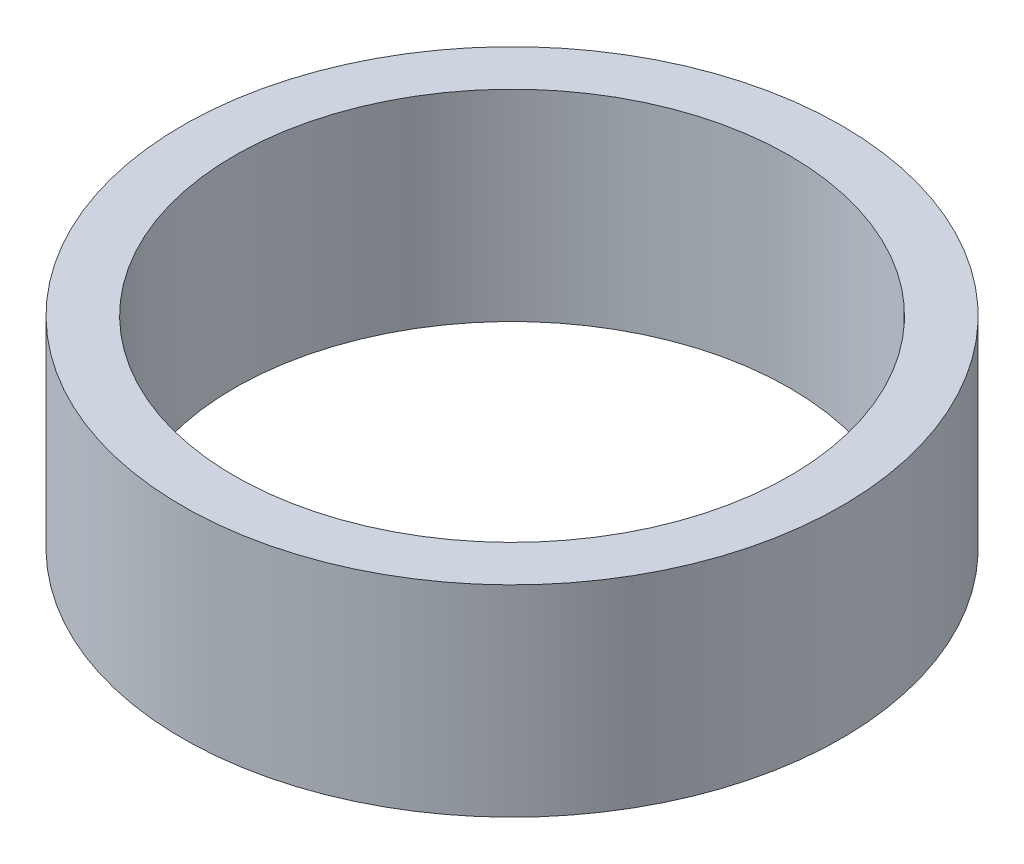
SolidWorks part; units mm, degrees
ref_plane "Front Plane" through (0, 0, 0) normal (0, 0, 1) x (1, 0, 0)
ref_plane "Top Plane" through (0, 0, 0) normal (0, 1, 0) x (1, 0, 0)
ref_plane "Right Plane" through (0, 0, 0) normal (1, 0, 0) x (0, 0, -1)
sketch "Sketch1" plane through (0, 0, 0) normal (0, 1, 0) x (1, 0, 0)
  circle A0 centre (0, 0) radius 47.5
  dimension "FLANGE_OD" = 95
extrude "Boss-Extrude1" add sketch "Sketch1" along normal blind 29
sketch "Sketch2" plane through (0, 0, 0) normal (0, 1, 0) x (1, 0, 0)
  circle A0 centre (0, 0) radius 40
  dimension "BORE_D" = 80
extrude "Cut-Extrude1" cut sketch "Sketch2" along normal through all
sketch "Sketch3" plane through (0, 29, 0) normal (0, 1, 0) x (1, 0, 0)
  circle A0 centre (0, 0) radius 21.5745 construction
  circle A1 centre (-21.5745, 0) radius 1.5
  dimension "BOLT_D" = 3
  dimension "BOLT_PCD" = 43.149
extrude "Cut-Extrude2" cut sketch "Sketch3" against normal blind 22.0369 rebuild error yes
pattern_circular "CirPattern1" count 8 over 360 rebuild error yes
